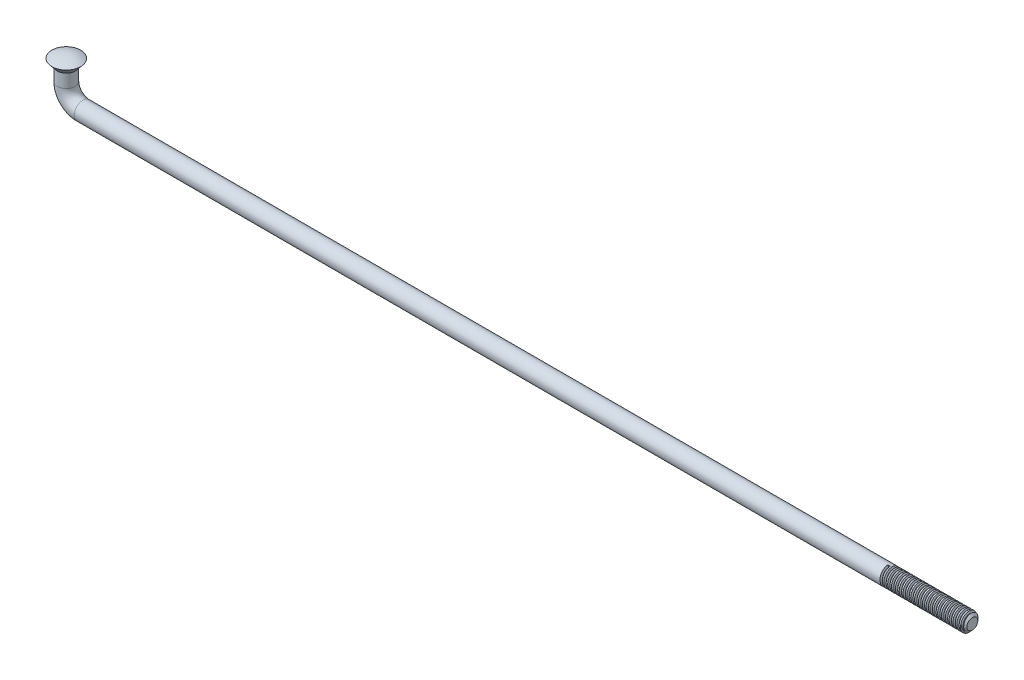
SolidWorks part; units mm, degrees
ref_plane "Front Plane" through (0, 0, 0) normal (0, 0, 1) x (1, 0, 0)
ref_plane "Top Plane" through (0, 0, 0) normal (0, 1, 0) x (1, 0, 0)
ref_plane "Right Plane" through (0, 0, 0) normal (1, 0, 0) x (0, 0, -1)
sketch "Sketch1" plane through (0, 0, 0) normal (0, 0, 1) x (1, 0, 0)
  line L0 (4.463, -1) -> (5.783, -1)
  line L1 (4.618, 0) -> (6.618, 0) construction
  line L2 (5.783, -1) -> (6.618, 0)
  line L3 (4.463, -1) -> (4.463, 0.4994)
  line L4 (4.463, 0.5) -> (4.463, -1) construction
  arc A0 (6.618, 0) -> (4.463, 0.4994) centre (4.6141, -3.7479) ccw
  dimension "D1" = 1.5
  dimension "D2" = 2
  dimension "D3" = 1.32
revolve "Revolve1" add sketch "Sketch1" angle 360 about L3
ref_plane "Plane1" through (0, 0, 0) normal (0, 0, 1) x (1, 0, 0)
sketch "Sketch2" plane through (0, 0, 0) normal (0, 0, 1) x (1, 0, 0)
  line L0 (4.463, -1) -> (4.463, -3)
  line L1 (3.143, -1) -> (5.783, -1) construction
  line L2 (6.963, -5.5) -> (140.463, -5.5)
  arc A0 (6.963, -5.5) -> (4.463, -3) centre (6.963, -3) cw
  point P9 (4.463, -5.5)
  dimension "D3" = 2.5
  dimension "D1" = 4.5
  dimension "D2" = 133.5
ref_plane "Plane2" through (140.463, -5.5, 0) normal (1, 0, 0) x (0, 0, -1)
sketch "Sketch3" plane through (140.463, -5.5, 0) normal (1, 0, 0) x (0, 0, -1)
  circle A0 centre (0, 0) radius 1.32
  dimension "D1" = 2.64
sweep "Sweep1" add profiles "Sketch3" path "Sketch2"
ref_plane "Plane3" through (140.463, 0, 0) normal (1, 0, 0) x (0, 0, -1)
sketch "Sketch4" plane through (140.463, 0, 0) normal (1, 0, 0) x (0, 0, -1)
  circle A0 centre (0, -5.5) radius 1.32
curve "Helix/Spiral1" pitch 0.5766 height 12.6848 radius 1.32 centre (140.463, -5.5, 0) axis (-1, 0, 0) start towards (0, 1, 0)
ref_plane "Plane4" through (0, 0, 0) normal (0, 0, 1) x (1, 0, 0)
sketch "Sketch6" plane through (0, 0, 0) normal (0, 0, 1) x (1, 0, 0)
  line L0 (140.463, -4.18) -> (140.588, -4.43)
  line L1 (140.463, -4.18) -> (140.638, -4.18)
  line L3 (140.638, -4.18) -> (140.813, -4.18)
  line L4 (140.688, -4.43) -> (140.813, -4.18)
  line L5 (140.638, -4.18) -> (140.638, -4.43) construction
  line L11 (140.588, -4.43) -> (140.688, -4.43)
  dimension "D1" = 26.565
sweep "Cut-Sweep1" cut profiles "Sketch6" path "Helix/Spiral1"
ref_plane "Plane5" through (0, 0, 0) normal (0, 0, 1) x (1, 0, 0)
sketch "Sketch7" plane through (0, 0, 0) normal (0, 0, 1) x (1, 0, 0)
  line L0 (139.9838, -4.17) -> (140.463, -4.6838)
  line L1 (140.463, -5.5) -> (137.8193, -5.5) construction
  line L4 (139.9838, -4.17) -> (140.463, -4.17)
  line L8 (140.463, -4.6838) -> (140.463, -4.17)
  dimension "D2" = 1.33
revolve "Cut-Revolve2" cut sketch "Sketch7" angle 360 about L1
ref_plane "Plane6" through (0, 0, 0) normal (0, 1, 0) x (-1, 0, 0)
sketch "Sketch8" plane through (0, 0, 0) normal (0, 1, 0) x (-1, 0, 0)
  line L0 (-4.463, 1.7375) -> (-4.463, -1.7375) construction
  line L1 (-6.2005, 0) -> (-2.7255, 0) construction
  circle A2 centre (-4.463, 0) radius 1.7375 construction
ref_plane "Plane7" through (0, 0, 0) normal (0, 0, 1) x (1, 0, 0)
sketch "Sketch9" plane through (0, 0, 0) normal (0, 0, 1) x (1, 0, 0)
  line L0 (2.308, 0) -> (6.618, 0)
  line L1 (6.618, 0) -> (5.783, -1)
  line L2 (5.783, -1) -> (3.143, -1)
  line L3 (3.143, -1) -> (2.308, 0)
  line L4 (3.143, -1) -> (3.143, -3)
  line L5 (5.783, -1) -> (5.783, -3)
  line L6 (6.963, -4.18) -> (127.7782, -4.18)
  line L7 (6.963, -6.82) -> (128.0665, -6.82)
  arc A0 (2.308, 0) -> (6.618, 0) centre (4.463, -4.4002) cw
  arc A1 (3.143, -3) -> (6.963, -6.82) centre (6.963, -3) ccw
  arc A2 (5.783, -3) -> (6.963, -4.18) centre (6.963, -3) ccw
